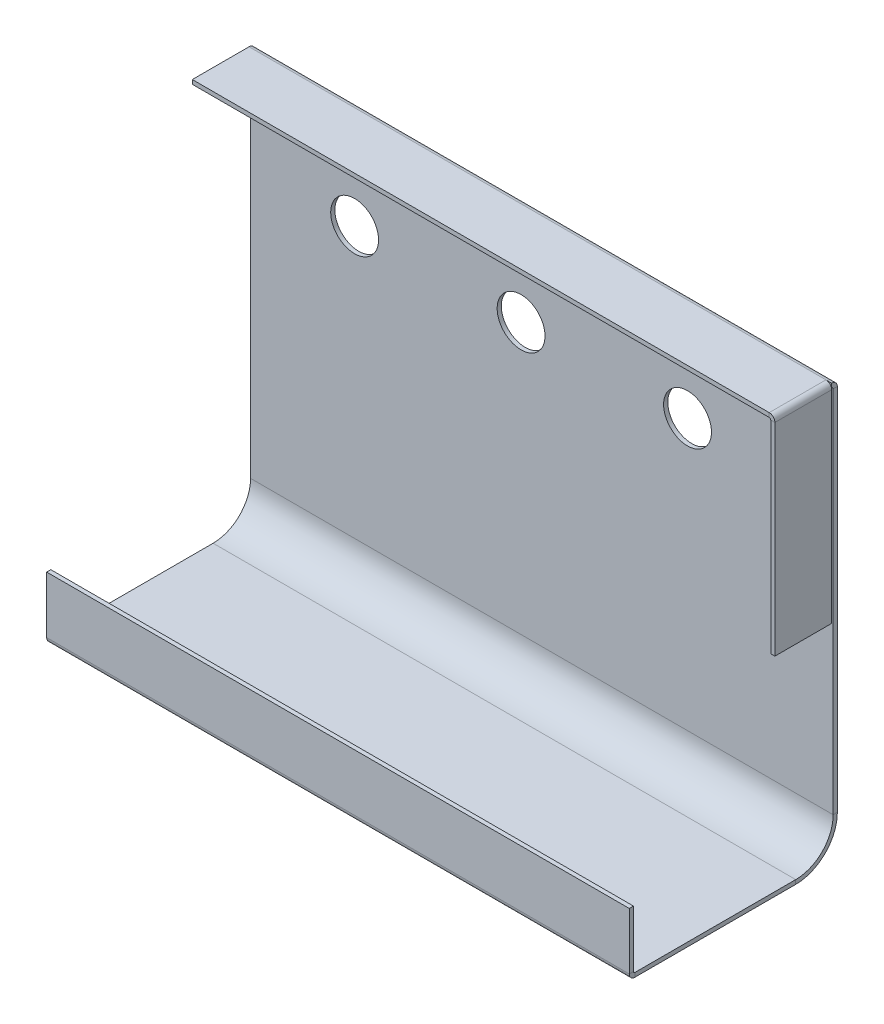
SolidWorks part; units mm, degrees
note: The reader was unsure of these and kept them because the rebuilt part matched: thickness of "基体-法兰1", "边线-法兰1", "边线-法兰2", "边线-法兰3", "边线-法兰4", "钣金6", "钣金7", "钣金8", "钣金11", "钣金14", "钣金18", "钣金19"; flange length of "边线-法兰1", "边线-法兰2", "边线-法兰3", "边线-法兰4".
ref_plane "前视基准面" through (0, 0, 0) normal (0, 0, 1) x (1, 0, 0)
ref_plane "上视基准面" through (0, 0, 0) normal (0, 1, 0) x (1, 0, 0)
ref_plane "右视基准面" through (0, 0, 0) normal (1, 0, 0) x (0, 0, -1)
sketch "草图2" plane through (0, 0, 0) normal (0, 0, 1) x (1, 0, 0)
  line L1 (-140, 100) -> (140, 100)
  line L2 (-140, 100) -> (-140, -100)
  line L3 (-140, -100) -> (140, -100)
  line L4 (140, 100) -> (140, -100)
  line L5 (-140, 100) -> (140, -100) construction
  line L6 (-140, -100) -> (140, 100) construction
  point P0 (0, 0)
  dimension "D1" = 280
  dimension "D2" = 200
base flange "基体-法兰1" sketch "草图2" thickness 2 reverse thickness direction no parameters "D1"=0.7366
edge flange "边线-法兰1" sketch "草图22" flange angle 90 flange length 100 flange position material inside bend radius 18 thickness 2 relief rectangular parameters "D6"=10
bend "边线折弯4" bend radius 18 bend angle 90 parameters "D5"=1
sketch "草图22" plane through (0, -100, 0) normal (0, 1, 0) x (-1, 0, 0)
  line L0 (-140, -2) -> (140, -2) construction
  line L1 (140, 0) -> (-140, 0) construction
  line L2 (-140, 0) -> (-140, 98)
  line L3 (-140, 98) -> (140, 98)
  line L4 (140, 98) -> (140, 0)
  line L5 (140, 0) -> (-140, 0)
  dimension "D1" = 100
edge flange "边线-法兰2" sketch "草图24" flange angle 90 flange length 30 flange position material inside bend radius 0.7366 thickness 2 relief rectangular parameters "D6"=10, "D8"=1
bend "边线折弯5" bend radius 0.7366 bend angle 90 parameters "D5"=2
sketch "草图24" plane through (0, 100, 0) normal (0, -1, 0) x (1, 0, 0)
  line L1 (140, 0) -> (-140, 0) construction
  line L2 (-140, 0) -> (-140, 28)
  line L3 (-140, 28) -> (140, 28)
  line L4 (140, 28) -> (140, 0)
  line L5 (140, 0) -> (-140, 0)
edge flange "边线-法兰3" sketch "草图27" flange angle 90 flange length 30 flange position material inside bend radius 0.7366 thickness 2 relief rectangular parameters "D6"=10
sketch "草图27" plane through (0, -98, 98) normal (0, 0, -1) x (-1, 0, 0)
  line L1 (140, 0) -> (-140, 0) construction
  line L2 (-140, 0) -> (-140, 28)
  line L3 (-140, 28) -> (140, 28)
  line L4 (140, 28) -> (140, 0)
  line L5 (140, 0) -> (-140, 0)
bend "边线折弯6" bend radius 0.7366 bend angle 90 parameters "D5"=3
sketch "草图28" plane through (0, 0, 98) normal (0, 0, 1) x (1, 0, 0)
sketch "草图36" plane through (0, 0, -2) normal (0, 0, -1) x (-1, 0, 0)
  line L0 (10, 50) -> (-70, 50) construction
  line L1 (140, 120) -> (10, 120) construction
  line L2 (140, 120) -> (140, 50) construction
  line L3 (140, 50) -> (10, 50) construction
  line L4 (10, 120) -> (10, 50) construction
  line L5 (140, 97.2634) -> (140, -80) construction
  line L6 (-140, 100) -> (140, 100) construction
  circle A0 centre (-70, 50) radius 11.5
  circle A1 centre (10, 50) radius 11.5
  circle A2 centre (90, 50) radius 11.5
  dimension "D4" = 23
  dimension "D5" = 23
  dimension "D6" = 23
  dimension "D1" = 80
  dimension "D2" = 80
  dimension "D3" = 70
  dimension "D7" = 50
  dimension "D8" = 50
extrude "切除-拉伸3" cut sketch "草图36" against normal blind 10 normal cut yes
edge flange "边线-法兰4" sketch "草图42" flange angle 90 flange length 100 flange position material inside bend radius 0.7366 thickness 2 relief none parameters "D6"=10
sketch "草图42" plane through (140, 98, 0) normal (1, 0, 0) x (0, 0, 1)
  line L0 (0.7366, 0) -> (28, 0) construction
  line L1 (0.7366, 0) -> (28, 0)
  line L2 (0.7366, 0) -> (0.7366, 98)
  line L3 (0.7366, 98) -> (28, 98)
  line L4 (28, 98) -> (28, 0)
bend "边线折弯7" bend radius 0.7366 bend angle 90 parameters "D5"=4
sketch "草图43" plane through (0, 0, 0) normal (0, 0, 1) x (1, 0, 0)
  circle A0 centre (107, 92) radius 2.5
  circle A1 centre (-113, 92) radius 2.5
hole_wizard "M4 螺纹孔1" positions "草图44" profile "草图45" tap size "M4" standard "GB" end condition through all
sketch "草图44" plane through (0, 0, -2) normal (0, 0, -1) x (-1, 0, 0)
  point P0 (-107, 92)
  point P3 (113, 92)
sketch "草图45" plane through (107, 92, -2) normal (1, 0, 0) x (0, 1, 0)
  line L0 (0, 0) -> (0, 100)
  line L1 (0, 100) -> (1.65, 100)
  line L2 (1.65, 100) -> (1.65, 0)
  line L5 (1.65, 0) -> (0, 0)
  line L11 (0, -6.35) -> (0, 107.95) construction
  dimension "通孔螺纹孔钻头直径" = 3.3
  dimension "通孔螺纹孔钻头深度" = 100
cosmetic thread "孔螺蚊线1"
cosmetic thread "孔螺蚊线2"
sketch "折弯-线1" plane through (0, 0, 0) normal (0, 1, 0) x (1, 0, 0)
sketch "边界框1" plane through (0, 0, 0) normal (0, 1, 0) x (1, 0, 0)
sheet metal parameters "钣金6" thickness 2 parameters "D1"=0.7366
flat pattern "平板型式6" [suppressed]
sketch "折弯-线2" plane through (0, 0, 0) normal (0, 1, 0) x (1, 0, 0)
sketch "边界框2" [suppressed] plane through (0, 0, 0) normal (0, 1, 0) x (1, 0, 0)
sheet metal parameters "钣金7" thickness 2 parameters "D1"=0.7366, "D7"=1.5
flat pattern "平板型式6" [suppressed]
sketch "折弯-线2" plane through (0, 0, 0) normal (0, 1, 0) x (1, 0, 0)
sketch "边界框2" [suppressed] plane through (0, 0, 0) normal (0, 1, 0) x (1, 0, 0)
bend of the flat pattern "展开-<边线折弯4>1"
sheet metal parameters "钣金8" thickness 2 parameters "D1"=0.7366, "D7"=1.5
flat pattern "平板型式6" [suppressed]
sketch "折弯-线2" plane through (0, 0, 0) normal (0, 1, 0) x (1, 0, 0)
sketch "边界框2" [suppressed] plane through (0, 0, 0) normal (0, 1, 0) x (1, 0, 0)
bend of the flat pattern "展开-<边线折弯4>2"
bend of the flat pattern "展开-<边线折弯5>1"
sheet metal parameters "钣金11" thickness 2 parameters "D1"=0.7366, "D7"=1.5
flat pattern "平板型式6" [suppressed]
sketch "折弯-线2" plane through (0, 0, 0) normal (0, 1, 0) x (1, 0, 0)
sketch "边界框2" [suppressed] plane through (0, 0, 0) normal (0, 1, 0) x (1, 0, 0)
bend of the flat pattern "展开-<边线折弯4>2"
bend of the flat pattern "展开-<边线折弯5>1"
bend of the flat pattern "展开-<边线折弯6>1"
sheet metal parameters "钣金14" thickness 2 parameters "D1"=0.7366, "D7"=1.5
flat pattern "平板型式6" [suppressed]
sketch "折弯-线2" plane through (0, 0, 0) normal (0, 0, 1) x (1, 0, 0)
  line L0 (-565, -107.0798) -> (565, -107.0798) construction
  line L1 (565, 38.02) -> (-565, 38.02) construction
  line L2 (-565, -34.5299) -> (565, -34.5299) construction
  line L3 (-565, -107.0798) -> (565, -107.0798) construction
  line L4 (565, 38.02) -> (-565, 38.02) construction
  line L5 (-565, -34.5299) -> (565, -34.5299) construction
sketch3d "边界框2" [suppressed]
  line L0 (-565, -155.0998, 0) -> (565, -155.0998, 0) construction
  line L1 (-565, 86.04, 0) -> (565, 86.04, 0) construction
  line L2 (-565, -155.0998, 0) -> (-565, 86.04, 0) construction
  line L3 (565, -155.0998, 0) -> (565, 86.04, 0) construction
bend of the flat pattern "展开-<边线折弯4>4"
bend of the flat pattern "展开-<边线折弯5>3"
bend of the flat pattern "展开-<边线折弯6>3"
sheet metal parameters "钣金18" thickness 2 parameters "D1"=0.7366, "D7"=1.5
flat pattern "平板型式6" [suppressed]
sketch "折弯-线2" plane through (0, 0, 0) normal (0, 0, 1) x (1, 0, 0)
  line L0 (-565, -107.0798) -> (565, -107.0798) construction
  line L1 (565, 38.02) -> (-565, 38.02) construction
  line L2 (-565, -34.5299) -> (565, -34.5299) construction
  line L3 (-565, -107.0798) -> (565, -107.0798) construction
  line L4 (565, 38.02) -> (-565, 38.02) construction
  line L5 (-565, -34.5299) -> (565, -34.5299) construction
sketch3d "边界框2" [suppressed]
  line L0 (-565, -155.0998, 0) -> (565, -155.0998, 0) construction
  line L1 (-565, 86.04, 0) -> (565, 86.04, 0) construction
  line L2 (-565, -155.0998, 0) -> (-565, 86.04, 0) construction
  line L3 (565, -155.0998, 0) -> (565, 86.04, 0) construction
bend of the flat pattern "展开-<边线折弯4>4"
bend of the flat pattern "展开-<边线折弯5>3"
bend of the flat pattern "展开-<边线折弯6>3"
bend of the flat pattern "展开-<边线折弯7>1"
sheet metal parameters "钣金19" thickness 2 parameters "D1"=0.7366, "D7"=1.5
flat pattern "平板型式6" [suppressed]
sketch "折弯-线2" plane through (0, 0, 0) normal (0, 0, 1) x (1, 0, 0)
  line L0 (-565, -107.0798) -> (565, -107.0798) construction
  line L1 (565, 38.02) -> (-565, 38.02) construction
  line L2 (-565, -34.5299) -> (565, -34.5299) construction
  line L3 (-565, -107.0798) -> (565, -107.0798) construction
  line L4 (565, 38.02) -> (-565, 38.02) construction
  line L5 (-565, -34.5299) -> (565, -34.5299) construction
sketch3d "边界框2" [suppressed]
  line L0 (-565, -155.0998, 0) -> (565, -155.0998, 0) construction
  line L1 (-565, 86.04, 0) -> (565, 86.04, 0) construction
  line L2 (-565, -155.0998, 0) -> (-565, 86.04, 0) construction
  line L3 (565, -155.0998, 0) -> (565, 86.04, 0) construction
bend of the flat pattern "展开-<边线折弯4>4"
bend of the flat pattern "展开-<边线折弯5>3"
bend of the flat pattern "展开-<边线折弯6>3"
bend of the flat pattern "展开-<边线折弯7>1"
